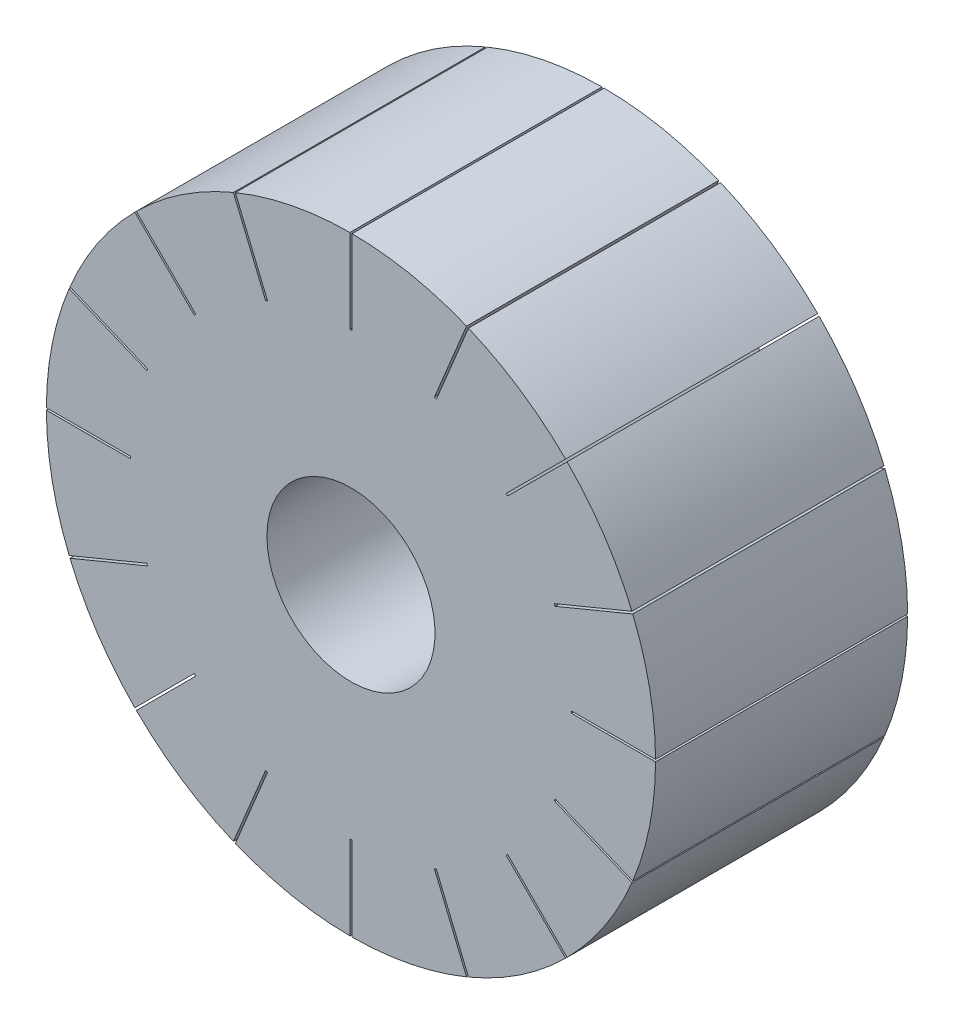
SolidWorks part; units mm, degrees
material "Cuivre"
ref_plane "Plan de face" through (0, 0, 0) normal (0, 0, 1) x (1, 0, 0)
ref_plane "Plan de dessus" through (0, 0, 0) normal (0, 1, 0) x (1, 0, 0)
ref_plane "Plan de droite" through (0, 0, 0) normal (1, 0, 0) x (0, 0, -1)
ref_axis "Axe1" through (0, 0, 0) along (0, 0, 1)
sketch "Esquisse1" plane through (0, 0, 0) normal (1, 0, 0) x (0, 0, -1)
  line L0 (0, 0) -> (-22.1316, 0) construction
  line L1 (-12, 4) -> (0, 4)
  line L3 (0, 4) -> (0, 14.5)
  line L4 (0, 14.5) -> (-12, 14.5)
  line L5 (-12, 4) -> (-12, 14.5)
  dimension "D1" = 29
  dimension "D2" = 12
  dimension "D3" = 8
revolve "Révolution1" add sketch "Esquisse1" angle 360 about L0
sketch "Esquisse2" plane through (0, 0, 0) normal (0, 0, 1) x (1, 0, 0)
  line L0 (0, 0) -> (0, 15.56) construction
  line L2 (-0.05, 14.5) -> (0.05, 14.5)
  line L3 (-0.05, 14.5) -> (-0.05, 10.5)
  line L4 (-0.05, 10.5) -> (0.05, 10.5)
  line L5 (0.05, 14.5) -> (0.05, 10.5)
  circle A0 centre (0, 0) radius 14.5 construction
  dimension "D1" = 4
  dimension "D2" = 0.1
extrude "Enlèv. mat.-Extru.2" cut sketch "Esquisse2" along normal through all
pattern_circular "Répétition circulaire1" count 16 over 360 about axis through (0, 0, 0) along (0, 0, 1) of "Enlèv. mat.-Extru.2"
